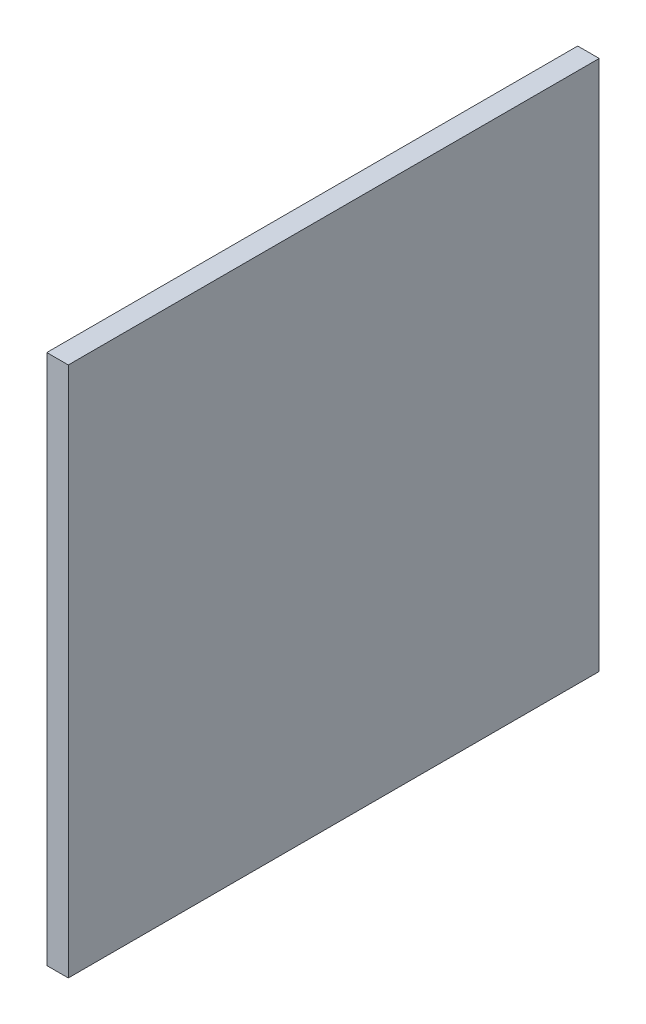
SolidWorks part; units mm, degrees
note: The reader was unsure of these and kept them because the rebuilt part matched: thickness of "Base-Flange1".
material "AISI 304"
ref_plane "Front Plane" through (0, 0, 0) normal (0, 0, 1) x (1, 0, 0)
ref_plane "Top Plane" through (0, 0, 0) normal (0, 1, 0) x (1, 0, 0)
ref_plane "Right Plane" through (0, 0, 0) normal (1, 0, 0) x (0, 0, -1)
sketch "Sketch1" plane through (0, 0, 0) normal (1, 0, 0) x (0, 0, -1)
  line L1 (37, -37) -> (-37, -37)
  line L2 (37, -37) -> (37, 37)
  line L3 (37, 37) -> (-37, 37)
  line L4 (-37, -37) -> (-37, 37)
  line L5 (37, -37) -> (-37, 37) construction
  line L6 (37, 37) -> (-37, -37) construction
  point P0 (0, 0)
  dimension "D1" = 74
base flange "Base-Flange1" sketch "Sketch1" thickness 3 reverse thickness direction no parameters "D1"=0.7366
sketch "Bend-Lines1" [suppressed] plane through (0, 0, 0) normal (0, 1, 0) x (1, 0, 0)
sketch "Bounding-Box1" [suppressed] plane through (0, 0, 0) normal (0, 1, 0) x (1, 0, 0)
sheet metal parameters "Sheet-Metal1" thickness 3 parameters "D1"=0.7366
flat pattern "Flat-Pattern1" [suppressed]
sketch "Bend-Lines2" plane through (0, 0, 0) normal (0, 1, 0) x (1, 0, 0)
sketch3d "Bounding-Box2" [suppressed]
  line L0 (-37, -37, 0) -> (37, -37, 0) construction
  line L1 (-37, 37, 0) -> (37, 37, 0) construction
  line L2 (-37, -37, 0) -> (-37, 37, 0) construction
  line L3 (37, -37, 0) -> (37, 37, 0) construction
equation "\"thickness 1\" = 2"
equation "\"thickness radius 1\"= 3.7366"
equation "\"thickness 2\"= 3"
equation "\"connecting flange\"= 35"
equation "\"main length\"= 1200"
equation "\"main width\"= 1200"
equation "\"divider panel distance offset\"= 296"
equation "\"top panel slot length\"= 250"
equation "\"top panel slot width\"= 700"
equation "\"side panel length\"= 1200"
equation "\"side panel width\"= 950"
equation "\"access hatch length\" = \"access hatch cutout length\" + \"access hatch offset\" * 2"
equation "\"access hatch width\" = \"access hatch cutout width\" + \"access hatch offset\" * 2"
equation "\"access hatch offset X\"= 100"
equation "\"access hatch offset Y\"= 100"
equation "\"back panel access hatch length\"= 1150"
equation "\"back panel access hatch width\"= 206"
equation "\"back panel access hatch flange\"= 40"
equation "\"slotted panel length\" = \"main length\" + 100"
equation "\"slotted panel width\" = \"main width\""
equation "\"slot count x\"= 4"
equation "\"slot count y\"= 9"
equation "\"slot offset\" = \"water tray depth\""
equation "\"slot length\"= 30"
equation "\"slot width\"= 200"
equation "\"slot offset x\" = \"slot length\" + \"slot offset\""
equation "\"slot offset y\" = \"slot width\" + \"slot offset\""
equation "\"drift eliminator size offset\"= 5"
equation "\"drift eliminator length\"= \"back panel access hatch length\" - \"drift eliminator size offset\""
equation "\"drift eliminator width\"= \"back panel access hatch width\" - \"drift eliminator size offset\""
equation "\"drift eliminator depth\" = \"divider panel distance offset\""
equation "\"guide rail flange\"= 40"
equation "\"guid rail flange mount side\"= 20"
equation "\"guid rail back length\" = \"main width\" - \"guide rail flange\" * 2"
equation "\"splash plate length\"= 400"
equation "\"splash plate width\" = \"main width\""
equation "\"splash plate air gap\"= 200"
equation "\"splash plate slot count\"= 11"
equation "\"splash plate slot length\"= 50"
equation "\"splash plate slot height\"= 50"
equation "\"splash plate slot offset\"= 65"
equation "\"water tray depth\"= 150"
equation "\"water tray width\"= 200"
equation "\"dimpled panel length\" = \"main length\" - 200 - \"water tray depth\"/2"
equation "\"dimpled panel top offset\" = \"water tray depth\"/2"
equation "\"dimpled panel width\" = \"main width\""
equation "\"dimple panel slot count\"= 36"
equation "\"dimple panel slot length\"= 8"
equation "\"dimple panel slot width\"= 8"
equation "\"dimple panel slot offset\"= 25"
equation "\"sump base flat section width\"= 300"
equation "\"sump upper depth\"= 300"
equation "\"sump depth\"= 550"
equation "\"leg length\" = \"sump depth\" + 150"
equation "\"leg width\"= 80"
equation "\"leg depth\"= 40"
equation "\"leg support plate size\" = \"leg width\" - \"thickness 2\" * 2"
equation "\"leg base plate thickness\"= 8"
equation "\"D1@Sketch1\"=\"leg support plate size\""
equation "\"D7@Sheet-Metal1\"=\"thickness 2\""
